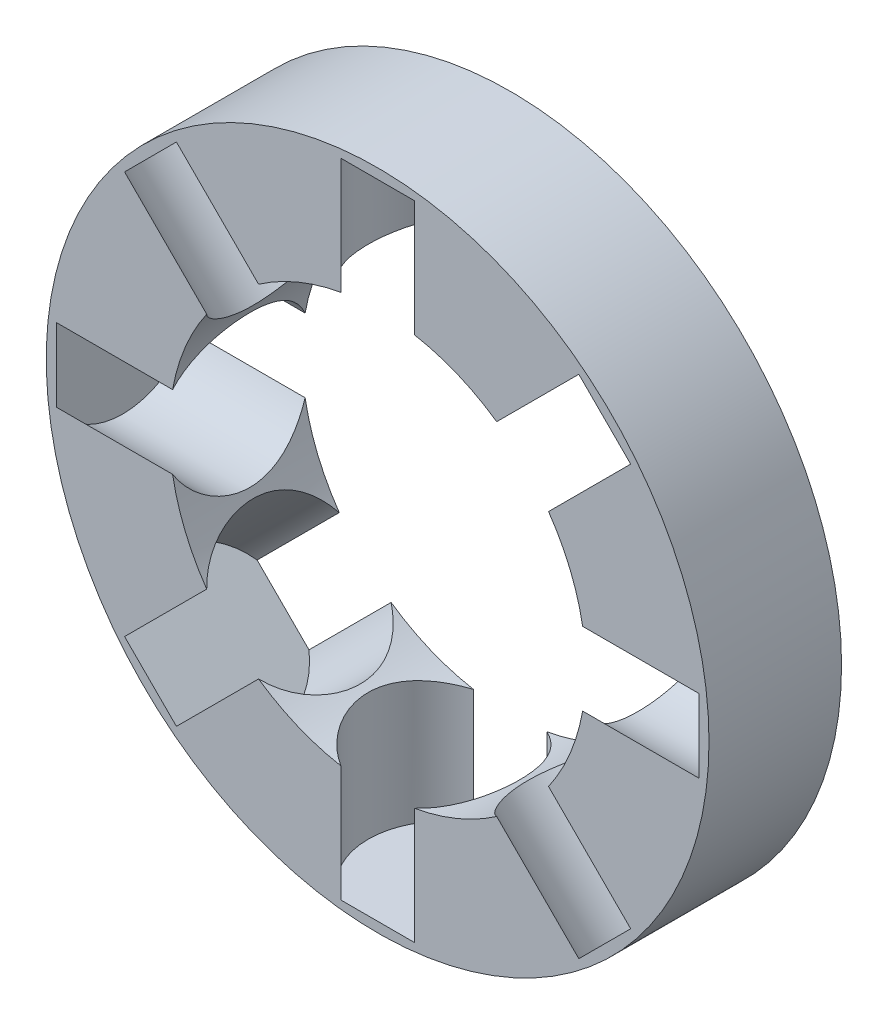
SolidWorks part; units mm, degrees
ref_plane "Top Plane" through (0, 0, 0) normal (0, 0, 1) x (1, 0, 0)
ref_plane "Right Plane" through (0, 0, 0) normal (0, 1, 0) x (1, 0, 0)
ref_plane "Front Plane" through (0, 0, 0) normal (1, 0, 0) x (0, 0, -1)
ref_axis "x-axis" through (-88.99, 0, 0) along (1, 0, 0)
ref_axis "y-axis" through (0, -55, 0) along (0, 1, 0)
ref_axis "z-axis" through (0, 0, 55) along (0, 0, -1)
sketch "Sketch1" plane through (0, 0, 0) normal (0, 0, 1) x (1, 0, 0)
  circle A0 centre (0, 0) radius 11
  circle A1 centre (0, 0) radius 17.5
  dimension "D1" = 22
  dimension "D2" = 6.5
extrude "Boss-Extrude1" add sketch "Sketch1" along normal mid plane 7
sketch "Sketch3" plane through (0, 0, 0) normal (0, 0, 1) x (1, 0, 0)
  line L0 (10.1627, -4.2095) -> (10.1627, 4.2095) construction
  line L1 (-10.1627, 4.2095) -> (-10.1627, -4.2095) construction
  line L2 (-10.1627, -4.2095) -> (-4.2095, -10.1627) construction
  line L3 (-4.2095, -10.1627) -> (4.2095, -10.1627) construction
  line L4 (4.2095, -10.1627) -> (10.1627, -4.2095) construction
  line L5 (10.1627, 4.2095) -> (4.2095, 10.1627) construction
  line L6 (4.2095, 10.1627) -> (-4.2095, 10.1627) construction
  line L7 (-4.2095, 10.1627) -> (-10.1627, 4.2095) construction
  line L8 (0, -55) -> (0, 55) construction
  circle A0 centre (0, 0) radius 10.1627 construction
  circle A2 centre (0, 0) radius 11 construction
  point P15 (0, 10.1627)
ref_plane "Plane1" through (-10.1627, 0, 0) normal (1, 0, 0) x (0, 0, -1)
sketch "Sketch4" plane through (-10.1627, 0, 0) normal (1, 0, 0) x (0, 0, -1)
  line L0 (0, 4.2095) -> (0, -4.2095) construction
  circle A0 centre (0, 0) radius 4
  dimension "D1" = 8
extrude "Cut-Extrude1" cut sketch "Sketch4" against normal blind 6.8
pattern_circular "CirPattern1" count 8 over 360 about axis through (0, 0, 3.5) along (0, 0, -1) of "Cut-Extrude1"
